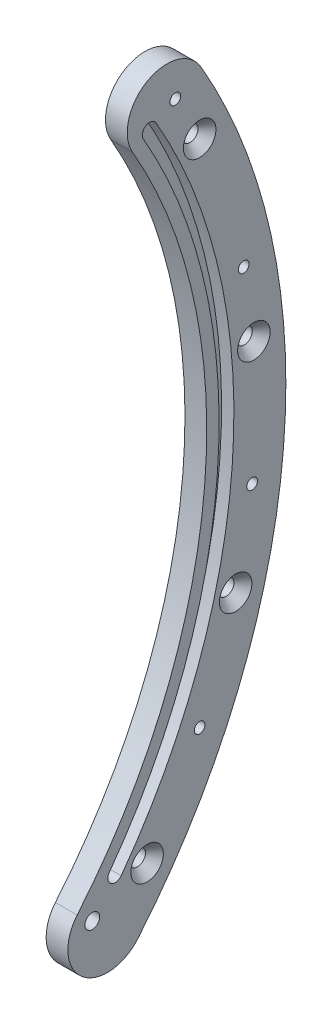
SolidWorks part; units mm, degrees
material "8619K441 HDPE"
ref_plane "Front" through (0, 0, 0) normal (0, 0, 1) x (1, 0, 0)
ref_plane "Top" through (0, 0, 0) normal (0, 1, 0) x (1, 0, 0)
ref_plane "Right" through (0, 0, 0) normal (1, 0, 0) x (0, 0, -1)
sketch "Sketch1" plane through (0, 0, 0) normal (1, 0, 0) x (0, 0, -1)
  line L0 (0, 50.8) -> (0, 177.8) construction
  line L1 (0, 0) -> (153.9793, 88.9) construction
  line L2 (0, 0) -> (136.2027, -114.2876) construction
  line L3 (0, 0) -> (177.8, 0) construction
  circle A0 centre (0, 0) radius 50.8 construction
  circle A1 centre (0, 0) radius 177.8 construction
  dimension "D1" = 101.6
  dimension "D2" = 127
  dimension "D3" = 60
  dimension "D4" = 70
sketch "Sketch2" plane through (0, 0, 0) normal (1, 0, 0) x (0, 0, -1)
  line L0 (0, 0) -> (136.2027, -114.2876) construction
  line L1 (0, 0) -> (153.9793, 88.9) construction
  arc A0 (153.9793, 88.9) -> (136.2027, -114.2876) centre (0, 0) cw
  arc A1 (136.2027, -114.2876) -> (155.6602, -130.6144) centre (145.9315, -122.451) ccw
  arc A2 (175.9764, 101.6) -> (153.9793, 88.9) centre (164.9778, 95.25) ccw
  arc A3 (155.6602, -130.6144) -> (175.9764, 101.6) centre (0, 0) ccw
  circle A4 centre (0, 0) radius 193.675 construction
  dimension "D1" = 25.4
  dimension "D2" = 387.35
extrude "Boss-Extrude1" add sketch "Sketch2" against normal mid plane 6.985
ref_axis "Axis1" through (80.9, 0, 0) along (-1, 0, 0)
ref_plane "Plane1" through (0, 0, 0) normal (-1, 0, 0) x (0, 0, 1)
ref_plane "Plane2" through (-3.4925, 0, 0) normal (1, 0, 0) x (0, 0, -1)
ref_plane "Plane3" through (3.4925, 0, 0) normal (-1, 0, 0) x (0, 0, 1)
sketch "Sketch3" plane through (3.4925, 0, 0) normal (-1, 0, 0) x (0, 0, 1)
  line L0 (0, 0) -> (-136.2027, -114.2876) construction
  line L1 (0, 0) -> (-153.9793, 88.9) construction
  arc A0 (-157.4164, 90.8844) -> (-161.5408, 93.2656) centre (-159.4786, 92.075) ccw
  circle A1 centre (-141.0671, -118.3693) radius 2.3813
  arc A2 (-158.2746, 94.1295) -> (-139.5247, -120.1835) centre (0, 0) ccw construction
  arc A3 (-157.4164, 90.8844) -> (-146.5022, -107.5964) centre (0, 0) ccw
  arc A4 (-161.5408, 93.2656) -> (-150.3407, -110.4155) centre (0, 0) ccw
  arc A5 (-150.3407, -110.4155) -> (-146.5022, -107.5964) centre (-148.4214, -109.006) ccw
  circle A6 centre (-141.0671, -118.3693) radius 9.525 construction
  dimension "D1" = 4.7625
  dimension "D2" = 184.15
  dimension "D3" = 19.05
extrude "Cut-Extrude1" cut sketch "Sketch3" against normal mid plane 7.9375 contours A4 A5 A3 A0 region at (3.4925, -10.0953, -183.5893)
hole_wizard "CSK for #10 Flat Head Socket Cap Screw1" positions "Sketch4" profile "Sketch6" countersink size "#10" standard "ANSI Inch" end condition through all
sketch "Sketch4" plane through (3.4925, 0, 0) normal (1, 0, 0) x (0, 0, -1)
  circle A0 centre (175.5292, 81.8506) radius 5.2197 construction
  circle A1 centre (192.938, 16.8799) radius 5.2197 construction
  circle A2 centre (187.0757, -50.1268) radius 5.2197 construction
  circle A3 centre (158.6493, -111.0874) radius 5.2197 construction
  point P0 (175.5292, 81.8506)
  point P2 (192.938, 16.8799)
  point P4 (187.0757, -50.1268)
  point P6 (158.6493, -111.0874)
sketch "Sketch6" plane through (3.4925, 81.8506, -175.5292) normal (0, 1, 0) x (0, 0, -1)
  line L0 (0, 0) -> (0, 6.985)
  line L1 (0, 6.985) -> (2.5527, 6.985)
  line L2 (2.5527, 6.985) -> (2.5527, 3.068)
  line L3 (2.5527, 3.068) -> (5.2197, 0)
  line L5 (5.2197, 0) -> (0, 0)
  line L6 (-2.5527, 3.068) -> (-5.2197, 0) construction
  line L11 (0, -6.35) -> (0, 107.95) construction
  dimension "Thru Hole Dia." = 5.1054
  dimension "Thru Hole Depth" = 6.985
  dimension "Near C'Sink Dia." = 10.4394
  dimension "Near C'Sink Angle" = 82
extrude "Cut-Extrude2" cut sketch "Sketch3<3>" against normal through all and the other way through all contours A1
sketch "Sketch3<3>" plane through (3.4925, 0, 0) normal (-1, 0, 0) x (0, 0, 1) same geometry as "Sketch3"
hole_wizard "#8-32 Tapped Hole2" positions "Sketch9" profile "Sketch11" tap size "#8-32" standard "ANSI Inch" end condition through all
sketch "Sketch9" plane through (3.4925, 0, 0) normal (1, 0, 0) x (0, 0, -1)
  circle A0 centre (192.3654, -22.4843) radius 2.2479 construction
  circle A1 centre (175.5292, -81.8506) radius 2.2479 construction
  circle A2 centre (189.6738, 39.1645) radius 2.2479 construction
  circle A3 centre (167.7275, 96.8375) radius 2.2479 construction
  point P0 (167.7275, 96.8375)
  point P2 (189.6738, 39.1645)
  point P4 (175.5292, -81.8506)
  point P6 (192.3654, -22.4843)
sketch "Sketch11" plane through (3.4925, 96.8375, -167.7275) normal (0, 1, 0) x (0, 0, -1)
  line L0 (0, 0) -> (0, 6.985)
  line L1 (0, 6.985) -> (1.7272, 6.985)
  line L2 (1.7272, 6.985) -> (1.7272, 0)
  line L5 (1.7272, 0) -> (0, 0)
  line L11 (0, -6.35) -> (0, 107.95) construction
  dimension "Thru Tap Drill Dia." = 3.4544
  dimension "Thru Tap Drill Depth" = 6.985
cosmetic thread "Hole Thread5" parameters "D2"=4.1656
cosmetic thread "Hole Thread6" parameters "D2"=4.1656
cosmetic thread "Hole Thread7" parameters "D2"=4.1656
cosmetic thread "Hole Thread8" parameters "D2"=4.1656
